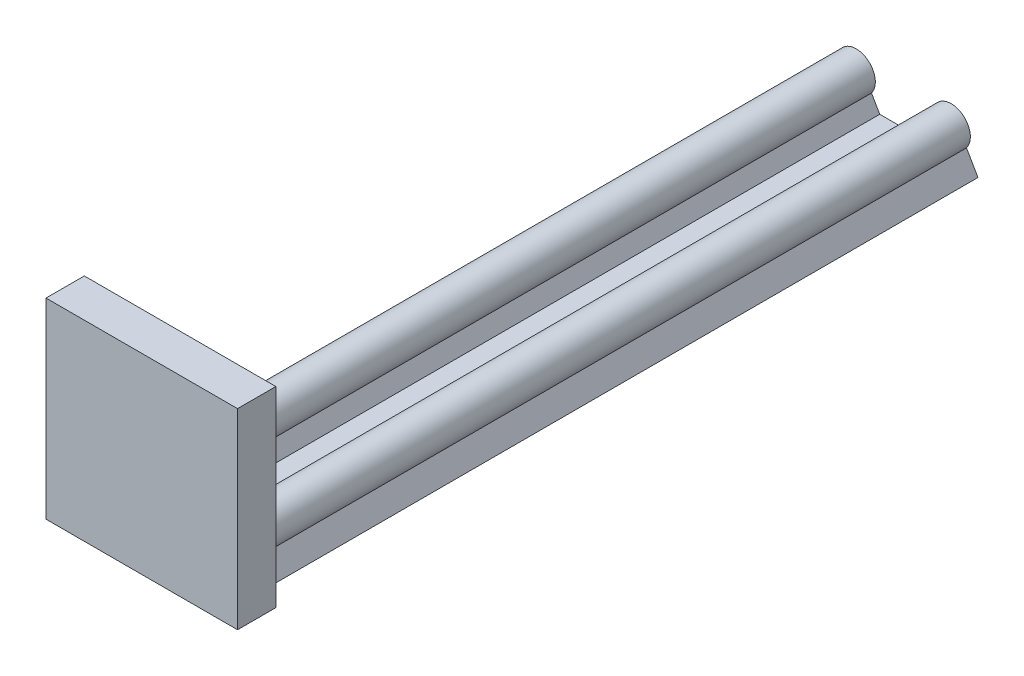
SolidWorks part; units mm, degrees
ref_plane "Front Plane" through (0, 0, 0) normal (0, 0, 1) x (1, 0, 0)
ref_plane "Top Plane" through (0, 0, 0) normal (0, 1, 0) x (1, 0, 0)
ref_plane "Right Plane" through (0, 0, 0) normal (1, 0, 0) x (0, 0, -1)
sketch "Sketch1" plane through (0, 0, 0) normal (0, 0, 1) x (1, 0, 0)
  line L0 (-4, -3) -> (4, -3) construction
  line L1 (-4, -3) -> (-7, -8.1962)
  line L2 (4, -3) -> (7, -8.1962)
  line L3 (-7, -8.1962) -> (7, -8.1962)
  line L4 (28.8, -3) -> (31.8, -8.1962)
  line L5 (17.8, -8.1962) -> (31.8, -8.1962)
  line L6 (20.8, -3) -> (17.8, -8.1962)
  circle A0 centre (0, 0) radius 5
  arc A1 (-4, -3) -> (4, -3) centre (0, 0) cw
  arc A2 (20.8, -3) -> (28.8, -3) centre (24.8, 0) cw
  dimension "D1" = 3
  dimension "D2" = 2
  dimension "D3" = 8
extrude "Boss-Extrude1" add sketch "Sketch1" along normal blind 220 contours A0 L0 | L0 A0 | A0 L1 L3 L2 | L4 L5 L6 A2 region at (0, 0.6334, 0) region at (0, -6.3253, 0) region at (0, -3.8155, 0)
sketch "Sketch3" plane through (0, 0, 220) normal (0, 0, 1) x (1, 0, 0)
  line L0 (7, -8.1962) -> (17.8, -8.1962)
  line L1 (6.15, -6.7239) -> (18.65, -6.7239)
  line L2 (4, -3) -> (7, -8.1962) construction
  line L3 (20.8, -3) -> (17.8, -8.1962) construction
  line L4 (18.65, -6.7239) -> (18.65, -8.1962)
  line L5 (17.8, -8.1962) -> (31.8, -8.1962) construction
  line L6 (18.65, -8.1962) -> (17.8, -8.1962)
  line L7 (6.15, -6.7239) -> (6.15, -8.1962)
  line L8 (-7, -8.1962) -> (7, -8.1962) construction
  line L9 (6.15, -8.1962) -> (7, -8.1962)
  dimension "D1" = 12.5
sketch "Sketch4" plane through (0, -8.1962, 0) normal (0, -1, 0) x (1, 0, 0)
  line L0 (24.8, 220) -> (24.8, 0) construction
  line L1 (17.8, 220) -> (31.8, 220) construction
  line L2 (17.8, 0) -> (31.8, 0) construction
  line L3 (0, 0) -> (0, 220) construction
  line L4 (-7, 220) -> (7, 220) construction
  circle A0 centre (0, 197.5) radius 3.2
  circle A1 centre (24.8, 197.5) radius 3.2
  circle A2 centre (24.8, 172.6) radius 3.2
  circle A3 centre (24.8, 147.7) radius 3.2
  circle A4 centre (24.8, 122.8) radius 3.2
  circle A5 centre (24.8, 97.9) radius 3.2
  circle A6 centre (24.8, 73) radius 3.2
  circle A7 centre (24.8, 48.1) radius 3.2
  circle A8 centre (24.8, 23.2) radius 3.2
  circle A9 centre (0, 172.6) radius 3.2
  circle A10 centre (0, 147.7) radius 3.2
  circle A11 centre (0, 122.8) radius 3.2
  circle A12 centre (0, 97.9) radius 3.2
  circle A13 centre (0, 73) radius 3.2
  circle A14 centre (0, 48.1) radius 3.2
  circle A15 centre (0, 23.2) radius 3.2
  dimension "D1" = 2
  dimension "D3" = 23.2
  dimension "D2" = 8
extrude "Boss-Extrude3" [suppressed] add sketch "Sketch4" along normal blind 6
extrude "Boss-Extrude4" add sketch "Sketch3" against normal blind 220
sketch "Sketch5" plane through (0, 0, 0) normal (0, 0, -1) x (-1, 0, 0)
  circle A0 centre (0, 0) radius 1.37
  circle A1 centre (-24.8, 0) radius 1.37
  dimension "D1" = 2
extrude "Cut-Extrude1" cut sketch "Sketch5" against normal blind 7
sketch "Sketch6" plane through (0, 0, 220) normal (0, 0, 1) x (1, 0, 0)
  circle A0 centre (0, 0) radius 1.37
  circle A1 centre (24.8, 0) radius 1.37
  dimension "D1" = 2
extrude "Cut-Extrude2" cut sketch "Sketch6" against normal blind 7
sketch "Sketch7" [suppressed] plane through (0, -14.1962, 0) normal (0, -1, 0) x (1, 0, 0)
  circle A0 centre (0, 172) radius 3.2
  circle A1 centre (24.8, 172) radius 3.2
  circle A2 centre (24.8, 147.2) radius 3.2
  circle A3 centre (24.8, 122.4) radius 3.2
  circle A4 centre (24.8, 97.6) radius 3.2
  circle A5 centre (24.8, 72.8) radius 3.2
  circle A6 centre (24.8, 48) radius 3.2
  circle A7 centre (0, 147.2) radius 3.2
  circle A8 centre (0, 122.4) radius 3.2
  circle A9 centre (0, 97.6) radius 3.2
  circle A10 centre (0, 72.8) radius 3.2
  circle A11 centre (0, 48) radius 3.2
  dimension "D1" = 2
  dimension "D2" = 6
extrude "Cut-Extrude3" [suppressed] cut sketch "Sketch7" against normal blind 6
sketch "Sketch9" plane through (0, 0, 0) normal (0, 0, -1) x (-1, 0, 0)
  line L6 (-28.8, -3) -> (-31.8, -8.1962)
  line L7 (-31.8, -8.1962) -> (7, -8.1962)
  line L8 (7, -8.1962) -> (4, -3)
  line L9 (-4, -3) -> (-6.15, -6.7239)
  line L10 (-6.15, -6.7239) -> (-18.65, -6.7239)
  line L11 (-18.65, -6.7239) -> (-20.8, -3)
  line L12 (-28.8, -3) -> (-31.8, -8.1962)
  line L13 (-31.8, -8.1962) -> (7, -8.1962)
  line L14 (7, -8.1962) -> (4, -3)
  line L15 (-4, -3) -> (-6.15, -6.7239)
  line L16 (-6.15, -6.7239) -> (-18.65, -6.7239)
  line L17 (-18.65, -6.7239) -> (-20.8, -3)
  arc A2 (4, -3) -> (-4, -3) centre (0, 0) ccw
  arc A3 (-20.8, -3) -> (-28.8, -3) centre (-24.8, 0) ccw
  arc A4 (4, -3) -> (-4, -3) centre (0, 0) ccw
  arc A5 (-20.8, -3) -> (-28.8, -3) centre (-24.8, 0) ccw
  dimension "D1" = 0
extrude "Cut-Extrude4" cut sketch "Sketch9" against normal blind 10.8
sketch "Sketch10" plane through (0, 0, 220) normal (0, 0, 1) x (1, 0, 0)
  line L6 (20.8, -3) -> (18.65, -6.7239)
  line L7 (18.65, -6.7239) -> (6.15, -6.7239)
  line L8 (6.15, -6.7239) -> (4, -3)
  line L9 (-4, -3) -> (-7, -8.1962)
  line L10 (-7, -8.1962) -> (31.8, -8.1962)
  line L11 (31.8, -8.1962) -> (28.8, -3)
  line L12 (20.8, -3) -> (18.65, -6.7239)
  line L13 (18.65, -6.7239) -> (6.15, -6.7239)
  line L14 (6.15, -6.7239) -> (4, -3)
  line L15 (-4, -3) -> (-7, -8.1962)
  line L16 (-7, -8.1962) -> (31.8, -8.1962)
  line L17 (31.8, -8.1962) -> (28.8, -3)
  arc A2 (4, -3) -> (-4, -3) centre (0, 0) ccw
  arc A3 (28.8, -3) -> (20.8, -3) centre (24.8, 0) ccw
  arc A4 (4, -3) -> (-4, -3) centre (0, 0) ccw
  arc A5 (28.8, -3) -> (20.8, -3) centre (24.8, 0) ccw
  dimension "D1" = 0
extrude "Cut-Extrude5" cut sketch "Sketch10" against normal blind 10.8
sketch "Sketch11" plane through (0, 0, 209.2) normal (0, 0, 1) x (1, 0, 0)
  circle A0 centre (0, 0) radius 2
  circle A1 centre (24.8, 0) radius 2
  dimension "D1" = 2
extrude "Cut-Extrude6" cut sketch "Sketch11" against normal blind 7
sketch "Sketch12" plane through (0, 0, 10.8) normal (0, 0, -1) x (-1, 0, 0)
  circle A0 centre (0, 0) radius 1.5
  circle A1 centre (-24.8, 0) radius 1.5
  dimension "D1" = 2
  dimension "D2" = 3
extrude "Cut-Extrude7" cut sketch "Sketch12" against normal blind 7
sketch "Sketch13" plane through (0, 0, 209.2) normal (0, 0, 1) x (1, 0, 0)
  line L0 (-7, -8.1962) -> (31.8, -8.1962) construction
  line L1 (-12.6, 41.8038) -> (37.4, 41.8038)
  line L2 (-12.6, 41.8038) -> (-12.6, -8.1962)
  line L3 (-12.6, -8.1962) -> (37.4, -8.1962)
  line L4 (37.4, 41.8038) -> (37.4, -8.1962)
  point P8 (12.4, -8.1962)
  point P9 (12.4, -8.1962)
  dimension "D1" = 50
  dimension "D2" = 50
extrude "Boss-Extrude5" add sketch "Sketch13" against normal blind 10
sketch "Sketch14" plane through (0, 0, 199.2) normal (0, 0, -1) x (-1, 0, 0)
  line L0 (-12.4, -8.1962) -> (-12.4, 41.8038) construction
  line L1 (-31.8, -8.1962) -> (7, -8.1962) construction
  line L2 (-37.4, 41.8038) -> (12.6, 41.8038) construction
  circle A0 centre (-12.4, 22.3038) radius 5
  dimension "D2" = 10
  dimension "D1" = 30.5
extrude "Cut-Extrude8" cut sketch "Sketch14" against normal blind 5
extrude "Cut-Extrude9" cut sketch "Sketch4<2>" against normal blind 5 contours A1 | A8 | A15 | A0 region at (24.8, -8.1962, 197.5)
sketch "Sketch4<2>" plane through (0, -8.1962, 0) normal (0, -1, 0) x (1, 0, 0) same geometry as "Sketch4"
sketch "Sketch16" plane through (0, 0, 10.8) normal (0, 0, -1) x (-1, 0, 0)
  line L0 (-31.8, -8.1962) -> (7, -8.1962) construction
  line L1 (-20.8, -3) -> (-18.65, -6.7239) construction
  line L2 (4, -3) -> (7, -8.1962) construction
  line L3 (-4, -3) -> (-6.15, -6.7239) construction
  line L4 (-6.15, -6.7239) -> (-18.65, -6.7239) construction
  line L5 (-28.8, -3) -> (-31.8, -8.1962) construction
  line L6 (-31.8, -8.1962) -> (7, -8.1962)
  line L7 (-20.8, -3) -> (-18.65, -6.7239)
  line L8 (4, -3) -> (7, -8.1962)
  line L9 (-4, -3) -> (-6.15, -6.7239)
  line L10 (-6.15, -6.7239) -> (-18.65, -6.7239)
  line L11 (-28.8, -3) -> (-31.8, -8.1962)
  circle A0 centre (0, 0) radius 1.5 construction
  circle A1 centre (-24.8, 0) radius 1.5 construction
  arc A2 (-20.8, -3) -> (-28.8, -3) centre (-24.8, 0) ccw construction
  arc A3 (4, -3) -> (-4, -3) centre (0, 0) ccw construction
  circle A4 centre (0, 0) radius 1.5
  circle A5 centre (-24.8, 0) radius 1.5
  arc A6 (-20.8, -3) -> (-28.8, -3) centre (-24.8, 0) ccw
  arc A7 (4, -3) -> (-4, -3) centre (0, 0) ccw
  circle A8 centre (-24.8, 0) radius 1.5
  circle A9 centre (0, 0) radius 1.5
extrude "Boss-Extrude7" add sketch "Sketch16" along normal blind 0.5 contours A2 L1 L2 L3 L4 L5 A0 A1 L0 A5 region at (29.9451, -5.803, 10.8)
